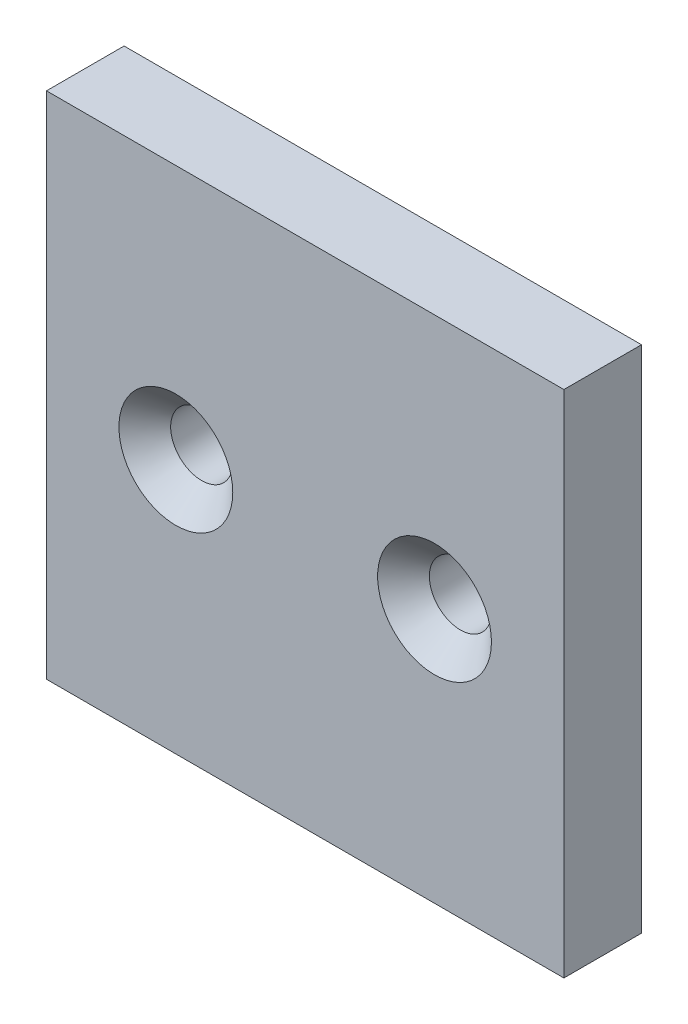
SolidWorks part; units mm, degrees
material "Gomma naturale"
ref_plane "Front" through (0, 0, 0) normal (0, 0, 1) x (1, 0, 0)
ref_plane "Top" through (0, 0, 0) normal (0, 1, 0) x (1, 0, 0)
ref_plane "Right" through (0, 0, 0) normal (1, 0, 0) x (0, 0, -1)
sketch "Schizzo1" plane through (0, 0, 0) normal (0, 0, 1) x (1, 0, 0)
  line L1 (0, 0) -> (20, 0)
  line L2 (0, 0) -> (0, 19.7)
  line L3 (0, 19.7) -> (20, 19.7)
  line L4 (20, 0) -> (20, 19.7)
  line L5 (0, 0) -> (20, 19.7) construction
  line L6 (0, 19.7) -> (20, 0) construction
  point P4 (10, 9.85)
extrude "Estrusione-Estrusione1" add sketch "Schizzo1" along normal blind 3
sketch "Schizzo2" plane through (0, 0, 3) normal (0, 0, 1) x (1, 0, 0)
  line L0 (0, 9.85) -> (5, 9.85)
  line L1 (0, 19.7) -> (0, 0) construction
  line L2 (5, 9.85) -> (15, 9.85)
  line L3 (15, 9.85) -> (20, 9.85)
  line L4 (20, 0) -> (20, 19.7) construction
hole_wizard "Foro svasato per Vite M2-2" positions "Schizzo5" profile "Schizzo6" countersink size "M2" standard "Ansi Metric" end condition through all
sketch "Schizzo5" plane through (0, 0, 3) normal (0, 0, 1) x (1, 0, 0)
  point P0 (5, 9.85)
  point P3 (15, 9.85)
sketch "Schizzo6" plane through (5, 9.85, 3) normal (1, 0, 0) x (0, -1, 0)
  line L0 (0, 0) -> (0, 3)
  line L1 (0, 3) -> (1.2, 3)
  line L2 (1.2, 3) -> (1.2, 1)
  line L3 (1.2, 1) -> (2.2, 0)
  line L5 (2.2, 0) -> (0, 0)
  line L6 (-1.2, 1) -> (-2.2, 0) construction
  line L11 (0, -6.35) -> (0, 107.95) construction
  dimension "Thru Hole Dia." = 2.4
  dimension "Thru Hole Depth" = 3
  dimension "Near C'Sink Dia." = 4.4
  dimension "Near C'Sink Angle" = 90
